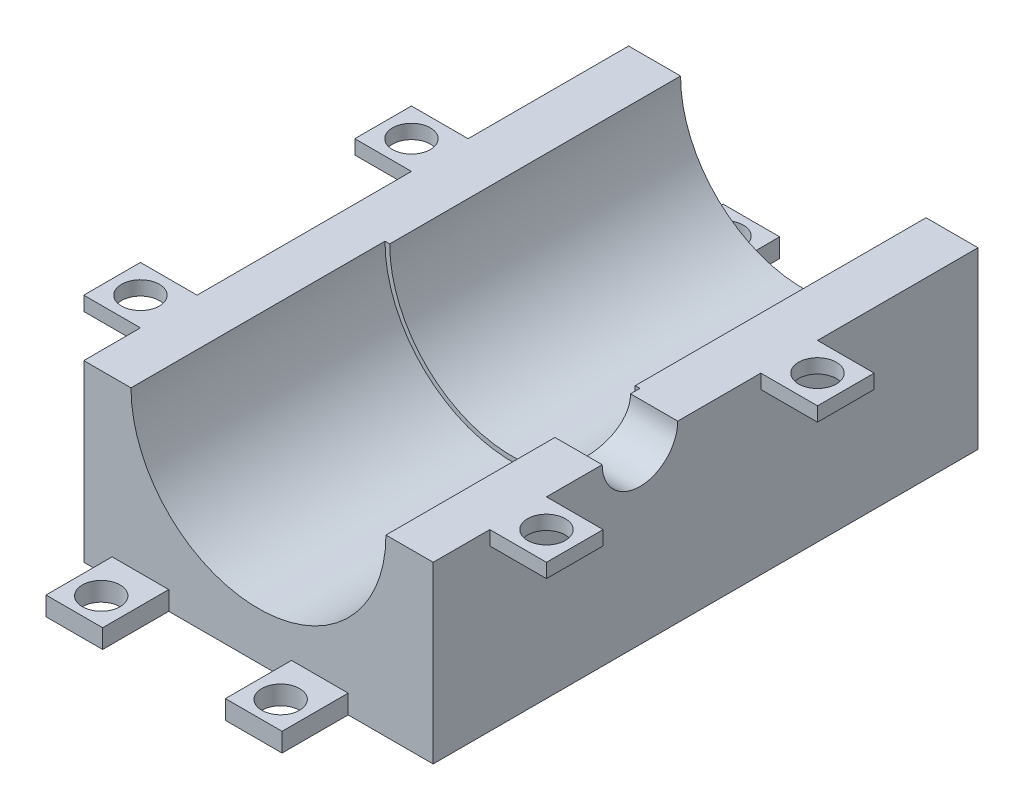
SolidWorks part; units mm, degrees
ref_plane "정면도" through (0, 0, 0) normal (0, 0, 1) x (1, 0, 0)
ref_plane "평면도" through (0, 0, 0) normal (0, 1, 0) x (1, 0, 0)
ref_plane "우측면도" through (0, 0, 0) normal (1, 0, 0) x (0, 0, -1)
sketch "스케치1" plane through (0, 0, 0) normal (0, 0, 1) x (1, 0, 0)
  line L0 (-13.5, 0) -> (-18.5, 0)
  line L1 (-18.5, 0) -> (-18.5, -18.5)
  line L2 (-18.5, -18.5) -> (18.5, -18.5)
  line L3 (18.5, -18.5) -> (18.5, 0)
  line L4 (18.5, 0) -> (13.5, 0)
  arc A0 (-13.5, 0) -> (13.5, 0) centre (0, 0) ccw
  arc A1 (-16, 0) -> (16, 0) centre (0, 0) ccw construction
  circle A2 centre (0, 0) radius 11.5
  point P9 (0, -16)
  dimension "D1" = 27
  dimension "D2" = 32
  dimension "D6" = 23
  dimension "D3" = 5
  dimension "D4" = 5
  dimension "D5" = 2.5
extrude "보스-돌출1" add sketch "스케치1" against normal blind 57.7 contours L1 L2 L3 L4 A0 L0
ref_plane "평면1" through (0, 0, -26.9) normal (0, 0, 1) x (1, 0, 0)
sketch "스케치3" plane through (0, 0, -26.9) normal (0, 0, 1) x (1, 0, 0)
  line L0 (-13.5, 0) -> (-11.5, 0)
  line L1 (13.5, 0) -> (11.5, 0)
  circle A0 centre (0, 0) radius 11.5 construction
  arc A1 (-11.5, 0) -> (11.5, 0) centre (0, 0) ccw
  arc A2 (-13.5, 0) -> (13.5, 0) centre (0, 0) ccw construction
  arc A3 (-13.5, 0) -> (13.5, 0) centre (0, 0) ccw
extrude "보스-돌출2" add sketch "스케치3" against normal blind 30.8
sketch "스케치5" plane through (18.5, 0, 0) normal (-1, 0, 0) x (0, 0, 1)
  line L0 (-57.7, 0) -> (0, 0) construction
  line L1 (0, 0) -> (0, -18.5) construction
  circle A0 centre (-21.9, 0) radius 4
  dimension "D2" = 8
  dimension "D1" = 21.9
extrude "컷-돌출1" cut sketch "스케치5" along normal blind 15
sketch "스케치7" plane through (0, -18.5, 0) normal (0, -1, 0) x (1, 0, 0)
  line L23 (-18.5, 0) -> (18.5, 0) construction
  line L24 (3.5, 7) -> (9.5, 7)
  line L30 (3.5, 7) -> (3.5, 0)
  line L31 (3.5, 0) -> (9.5, 0)
  line L36 (9.5, 7) -> (9.5, 0)
  line L37 (3.5, 0) -> (9.5, 7) construction
  line L43 (-15.5, 7) -> (-9.5, 7)
  line L44 (-15.5, 7) -> (-15.5, 0)
  line L45 (-15.5, 0) -> (-9.5, 0)
  line L46 (-9.5, 7) -> (-9.5, 0)
  line L47 (9.5, 0) -> (3.5, 7) construction
  line L48 (18.5, -57.7) -> (18.5, 0) construction
  line L50 (-15.5, 0) -> (-9.5, 7) construction
  line L51 (-9.5, 0) -> (-15.5, 7) construction
  circle A0 centre (6.5, 4.15) radius 2
  circle A1 centre (-12.5, 4.15) radius 2
  point P10 (6.5, 3.5)
  point P14 (-12.5, 7)
  point P20 (-12.5, 3.5)
  dimension "D7" = 4
  dimension "D8" = 4
  dimension "D1" = 12
  dimension "D2" = 7
  dimension "D3" = 19
  dimension "D4" = 7
  dimension "D5" = 6
  dimension "D6" = 6
  dimension "D9" = 0.65
  dimension "D10" = 0.65
extrude "보스-돌출3" add sketch "스케치7" against normal blind 2
ref_plane "평면2" through (0, 0, -28.85) normal (0, 0, 1) x (1, 0, 0)
mirror "대칭 복사1" about plane through (0, 0, -28.85) normal (0, 0, 1) of "보스-돌출3"
sketch "스케치8" plane through (-18.5, 0, 0) normal (-1, 0, 0) x (0, 0, 1)
  line L0 (-57.7, 0) -> (0, 0) construction
  line L1 (-34.7, -1.5) -> (-40.7, -1.5)
  line L2 (-34.7, -1.5) -> (-34.7, 1.5)
  line L3 (-34.7, 1.5) -> (-40.7, 1.5)
  line L4 (-40.7, -1.5) -> (-40.7, 1.5)
  line L5 (-37.7, 1.5) -> (-37.7, -1.5) construction
  line L6 (-34.7, 0) -> (-40.7, 0) construction
  line L7 (0, 0) -> (0, -18.5) construction
  line L8 (-12, -1.5) -> (-6, -1.5)
  line L9 (-12, -1.5) -> (-12, 1.5)
  line L10 (-12, 1.5) -> (-6, 1.5)
  line L11 (-6, -1.5) -> (-6, 1.5)
  line L12 (-9, 1.5) -> (-9, -1.5) construction
  line L13 (-12, 0) -> (-6, 0) construction
  line L14 (-57.7, 0) -> (-57.7, -18.5) construction
  line L15 (-40.7, 0) -> (-34.7, 0)
  line L16 (-12, 0) -> (-6, 0)
  point P0 (-37.7, 0)
  point P6 (-9, 0)
  line M6 (0, 0) -> (-57.7, 0)
  dimension "D1" = 9
  dimension "D2" = 20
  dimension "D3" = 6
  dimension "D4" = 3
  dimension "D5" = 6
  dimension "D6" = 3
extrude "보스-돌출4" add sketch "스케치8" along normal blind 6 contours L8 L11 L9 M6 | L4 L1 L2 M6 region at (-18.5, -0.75, -9) region at (-18.5, -0.75, -37.7)
extrude "보스-돌출5" add sketch "스케치8<3>" against normal blind 6 from surface contours L8 L11 L9 M6 | L4 L1 L2 M6 region at (-18.5, -0.75, -9) region at (-18.5, -0.75, -37.7) starting at face at (18.5, -6.8333, -26.5333)
sketch "스케치8<3>" plane through (-18.5, 0, 0) normal (-1, 0, 0) x (0, 0, 1) same geometry as "스케치8"
sketch "스케치9" plane through (0, 0, 0) normal (0, 1, 0) x (1, 0, 0)
  line L0 (-18.5, 40.7) -> (-24.5, 34.7) construction
  line L1 (-24.5, 40.7) -> (-18.5, 34.7) construction
  line L2 (-18.5, 12) -> (-24.5, 6) construction
  line L3 (-24.5, 12) -> (-18.5, 6) construction
  line L4 (0, 0) -> (0, 57.7) construction
  line L5 (11.5, 57.7) -> (-11.5, 57.7) construction
  circle A0 centre (-21.5, 37.7) radius 2
  circle A1 centre (-21.5, 9) radius 2
  circle A2 centre (21.5, 9) radius 2
  circle A3 centre (21.5, 37.7) radius 2
  dimension "D1" = 4
extrude "컷-돌출2" cut sketch "스케치9" against normal blind 6
sketch "스케치10" plane through (0, 0, -26.9) normal (0, 0, 1) x (1, 0, 0)
  circle A0 centre (0, 0) radius 13
  dimension "D1" = 26
extrude "컷-돌출3" cut sketch "스케치10" against normal through all
